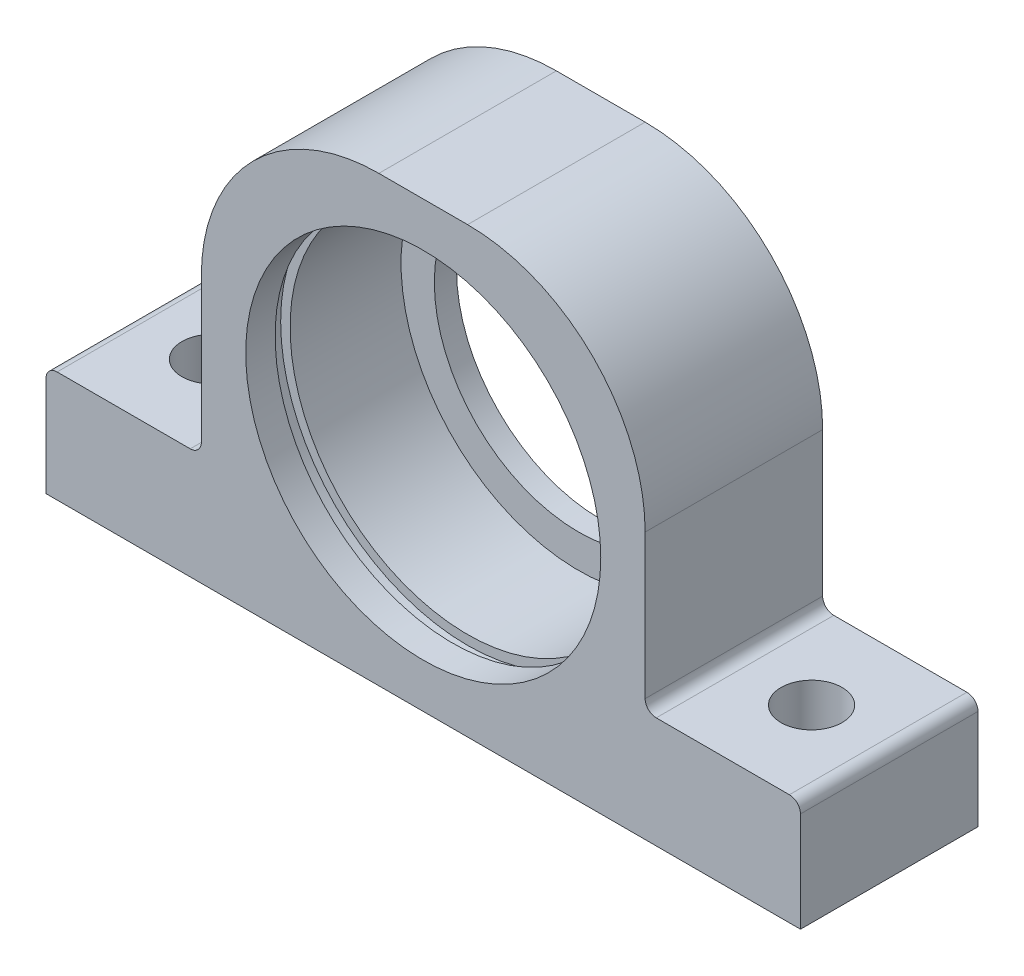
SolidWorks part; units mm, degrees
ref_plane "正面" through (0, 0, 0) normal (0, 0, 1) x (1, 0, 0)
ref_plane "平面" through (0, 0, 0) normal (0, 1, 0) x (1, 0, 0)
ref_plane "右側面" through (0, 0, 0) normal (1, 0, 0) x (0, 0, -1)
ref_plane "平面1" through (0, 0, 0) normal (0, 0, 1) x (1, 0, 0)
sketch "ｽｹｯﾁ1" plane through (0, 0, 0) normal (0, 0, 1) x (1, 0, 0)
  line L0 (-34, 9) -> (-34, 0)
  line L1 (-34, 0) -> (34, 0)
  line L2 (34, 0) -> (34, 9)
  line L3 (33, 10) -> (21, 10)
  line L4 (20, 11) -> (20, 24)
  line L5 (4, 40) -> (-4, 40)
  line L6 (-20, 24) -> (-20, 11)
  line L7 (-21, 10) -> (-33, 10)
  arc A0 (34, 9) -> (33, 10) centre (33, 9) ccw
  arc A1 (21, 10) -> (20, 11) centre (21, 11) cw
  arc A2 (20, 24) -> (4, 40) centre (4, 24) ccw
  arc A3 (-4, 40) -> (-20, 24) centre (-4, 24) ccw
  arc A4 (-20, 11) -> (-21, 10) centre (-21, 11) cw
  arc A5 (-33, 10) -> (-34, 9) centre (-33, 9) ccw
extrude "ﾎﾞｽ - 押し出し1" add sketch "ｽｹｯﾁ1" against normal blind 8 and the other way blind 8
ref_plane "平面2" through (0, 0, 0) normal (1, 0, 0) x (0, 0, -1)
sketch "ｽｹｯﾁ2" plane through (0, 0, 0) normal (1, 0, 0) x (0, 0, -1)
  line L0 (-8, 20) -> (-8, 36)
  line L1 (-8, 36) -> (-5.35, 36)
  line L2 (-5.35, 36) -> (-5.35, 36.85)
  line L3 (-5.35, 36.85) -> (-4, 36.85)
  line L4 (-4, 36.85) -> (-4, 36)
  line L5 (-4, 36) -> (6, 36)
  line L6 (6, 36) -> (6, 33)
  line L7 (6, 33) -> (8, 33)
  line L8 (8, 33) -> (8, 20)
  line L9 (8, 20) -> (-8, 20)
  line L10 (8, 20) -> (-8, 20) construction
revolve "ｶｯﾄ - 回転1" cut sketch "ｽｹｯﾁ2" angle 360 about L10 reverse direction yes
ref_plane "平面3" through (0, 0, 0) normal (0, 0, 1) x (1, 0, 0)
sketch "ｽｹｯﾁ3" plane through (0, 0, 0) normal (0, 0, 1) x (1, 0, 0)
  line L0 (27, 10) -> (29.75, 10)
  line L1 (29.75, 10) -> (29.75, 0)
  line L2 (29.75, 0) -> (27, 0)
  line L3 (27, 0) -> (27, 10)
  line L4 (27, 0) -> (27, 10) construction
revolve "ｶｯﾄ - 回転2" cut sketch "ｽｹｯﾁ3" angle 360 about L4 reverse direction yes
ref_plane "平面4" through (0, 0, 0) normal (0, 0, 1) x (1, 0, 0)
sketch "ｽｹｯﾁ4" plane through (0, 0, 0) normal (0, 0, 1) x (1, 0, 0)
  line L0 (-27, 10) -> (-24.25, 10)
  line L1 (-24.25, 10) -> (-24.25, 0)
  line L2 (-24.25, 0) -> (-27, 0)
  line L3 (-27, 0) -> (-27, 10)
  line L4 (-27, 0) -> (-27, 10) construction
revolve "ｶｯﾄ - 回転3" cut sketch "ｽｹｯﾁ4" angle 360 about L4 reverse direction yes
